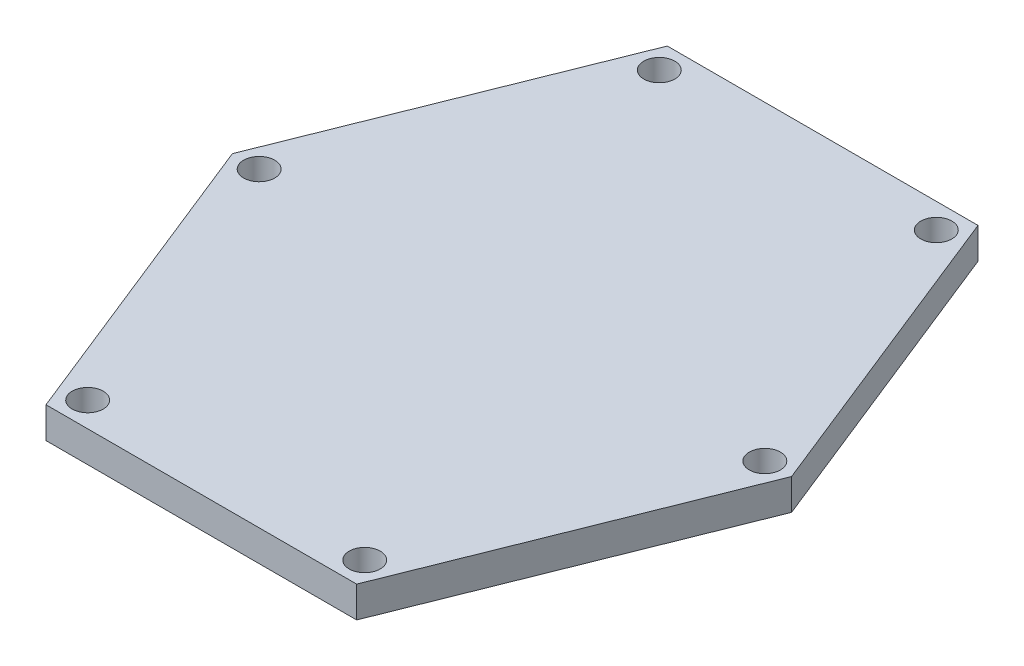
SolidWorks part; units mm, degrees
ref_plane "Front Plane" through (0, 0, 0) normal (0, 0, 1) x (1, 0, 0)
ref_plane "Top Plane" through (0, 0, 0) normal (0, 1, 0) x (1, 0, 0)
ref_plane "Right Plane" through (0, 0, 0) normal (1, 0, 0) x (0, 0, -1)
sketch "Sketch1" plane through (0, 0, 0) normal (0, 1, 0) x (1, 0, 0)
  line L0 (-25, 42.7373) -> (25, 42.7373)
  line L1 (25, 42.7373) -> (45, -7.2627)
  line L2 (45, -7.2627) -> (25, -57.2627)
  line L3 (25, -57.2627) -> (-25, -57.2627)
  line L4 (-25, -57.2627) -> (-45, -7.2627)
  line L5 (-45, -7.2627) -> (-25, 42.7373)
  point P2 (0, 0)
  point P7 (-45.3178, -1.9883)
  point P8 (0, -57.2627)
  point P10 (44.4893, -10.4388)
  dimension "D1" = 50
  dimension "D2" = 100
  dimension "D3" = 90
extrude "Boss-Extrude1" add sketch "Sketch1" along normal blind 5
sketch "Sketch2" plane through (0, 5, 0) normal (0, 1, 0) x (1, 0, 0)
  line L0 (25, 42.7373) -> (-25, 42.7373) construction
  line L1 (-25, 42.7373) -> (-45, -7.2627) construction
  line L2 (-45, -7.2627) -> (-25, -57.2627) construction
  line L3 (-25, -57.2627) -> (25, -57.2627) construction
  line L4 (25, -57.2627) -> (45, -7.2627) construction
  line L5 (45, -7.2627) -> (25, 42.7373) construction
  circle A0 centre (-22.2919, 38.7373) radius 4 construction
  circle A1 centre (22.2919, 38.7373) radius 4 construction
  circle A2 centre (40.6919, -7.2627) radius 4 construction
  circle A3 centre (22.2919, -53.2627) radius 4 construction
  circle A4 centre (-22.2919, -53.2627) radius 4 construction
  circle A5 centre (-40.6919, -7.2627) radius 4 construction
  circle A6 centre (-22.2919, 38.7373) radius 2.5
  circle A7 centre (22.2919, 38.7373) radius 2.5
  circle A8 centre (-40.6919, -7.2627) radius 2.5
  circle A9 centre (40.6919, -7.2627) radius 2.5
  circle A10 centre (-22.2919, -53.2627) radius 2.5
  circle A11 centre (22.2919, -53.2627) radius 2.5
  dimension "D1" = 8
  dimension "D2" = 5
extrude "Cut-Extrude1" cut sketch "Sketch2" against normal blind 5
